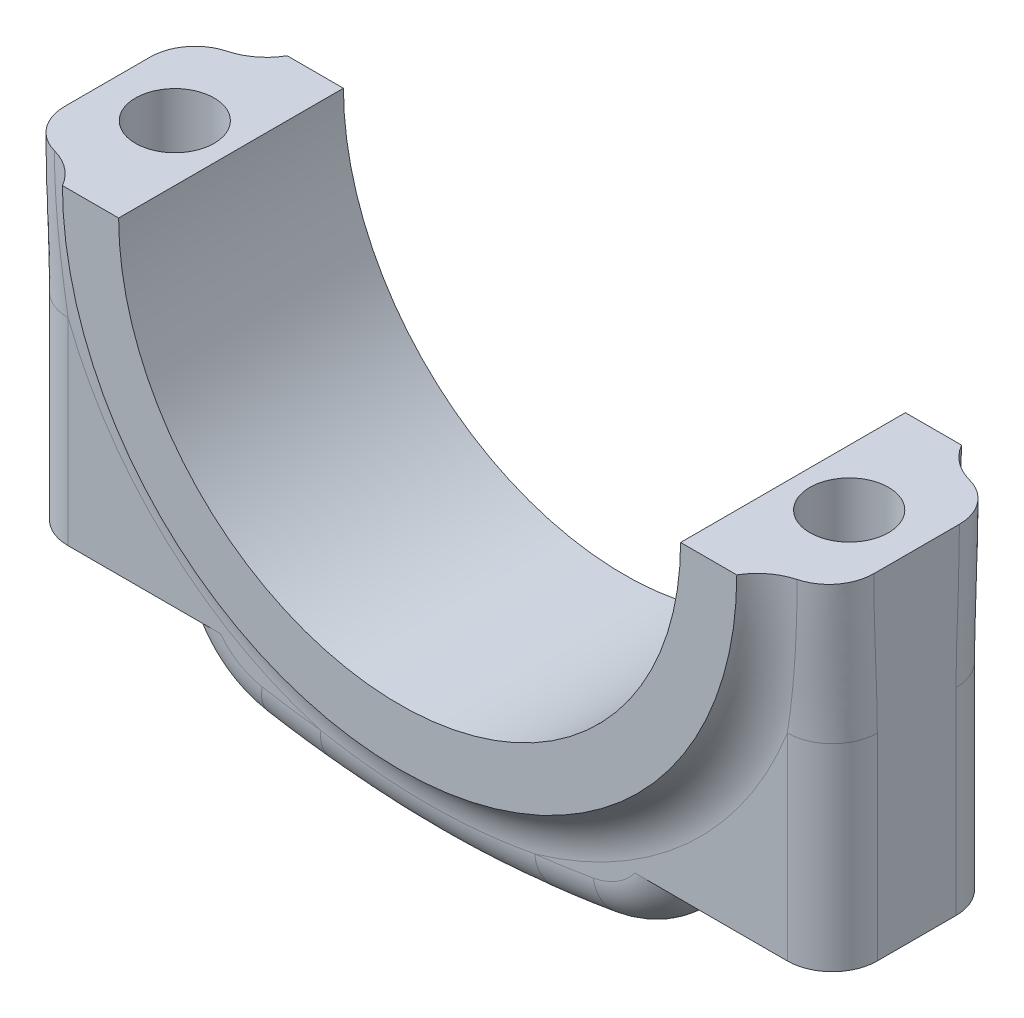
SolidWorks part; units mm, degrees
ref_plane "Front Plane" through (0, 0, 0) normal (0, 0, 1) x (1, 0, 0)
ref_plane "Top Plane" through (0, 0, 0) normal (0, 1, 0) x (1, 0, 0)
ref_plane "Right Plane" through (0, 0, 0) normal (1, 0, 0) x (0, 0, -1)
sketch "Sketch1" plane through (0, 0, 0) normal (0, 0, 1) x (1, 0, 0)
  line L0 (-36, 0) -> (-25, 0)
  line L1 (36, 0) -> (36, -30)
  line L2 (0, 0) -> (0, -25) construction
  line L3 (-36, 0) -> (-36, -30)
  line L4 (25, 0) -> (36, 0)
  arc A0 (-25, 0) -> (25, 0) centre (0, 0) ccw
  arc A1 (-36, -30) -> (36, -30) centre (0, 52.4864) ccw
  dimension "D3" = 50
  dimension "D4" = 180
  dimension "D1" = 36
  dimension "D2" = 30
extrude "Boss-Extrude1" add sketch "Sketch1" along normal mid plane 15
sketch "Sketch2" plane through (0, 0, 7.5) normal (0, 0, 1) x (1, 0, 0)
  line L0 (-30, 0) -> (-25, 0)
  line L1 (25, 0) -> (30, 0)
  arc A0 (-25, 0) -> (25, 0) centre (0, 0) ccw construction
  arc A1 (-25, 0) -> (25, 0) centre (0, 0) ccw
  arc A2 (-30, 0) -> (30, 0) centre (0, 0) ccw
  dimension "D1" = 60
extrude "Boss-Extrude2" add sketch "Sketch2" along normal blind 2.5
sketch "Sketch3" plane through (0, 0, -7.5) normal (0, 0, -1) x (-1, 0, 0)
  line L2 (30, 0) -> (25, 0)
  line L3 (-25, 0) -> (-30, 0)
  line L4 (30, 0) -> (25, 0)
  line L5 (-25, 0) -> (-30, 0)
  arc A2 (-25, 0) -> (25, 0) centre (0, 0) ccw
  arc A3 (-30, 0) -> (30, 0) centre (0, 0) ccw
  arc A4 (-25, 0) -> (25, 0) centre (0, 0) ccw
  arc A5 (-30, 0) -> (30, 0) centre (0, 0) ccw
  dimension "D1" = 0
extrude "Boss-Extrude3" add sketch "Sketch3" along normal blind 2.5
fillet "Fillet1" radius 5 2 edges at (0, -30, 7.5) (0, -30, -7.5)
hole_wizard "Ø7.0 (7) Diameter Hole1" positions "Sketch13" profile "Sketch14" hole size "Ø7.0" standard "ISO" end condition through all
sketch "Sketch13" plane through (0, 0, 0) normal (0, 1, 0) x (1, 0, 0)
  point P0 (30, 0)
  point P2 (-30, 0)
  dimension "D1" = 30
  dimension "D2" = 30
sketch "Sketch14" plane through (30, 0, 0) normal (1, 0, 0) x (0, 0, 1)
  line L0 (0, 0) -> (0, 37.5136)
  line L1 (0, 37.5136) -> (3.5, 37.5136)
  line L2 (3.5, 37.5136) -> (3.5, 0)
  line L5 (3.5, 0) -> (0, 0)
  line L11 (0, -6.35) -> (0, 107.95) construction
  dimension "Thru Hole Dia." = 7
  dimension "Thru Hole Depth" = 37.5136
ref_plane "Plane1" through (0, -30, 0) normal (0, 1, 0) x (1, 0, 0)
sketch "Sketch15" plane through (0, -30, 0) normal (0, 1, 0) x (1, 0, 0)
  line L0 (0, 0) -> (0, -14.9136) construction
  line L1 (23, -12.2006) -> (37.3058, -12.2006)
  line L2 (23, -12.2006) -> (23, 11.925)
  line L3 (23, 11.925) -> (37.3058, 11.925)
  line L4 (37.3058, -12.2006) -> (37.3058, 11.925)
  line L5 (-37.3058, -12.2006) -> (-37.3058, 11.925)
  line L6 (-23, 11.925) -> (-37.3058, 11.925)
  line L7 (-23, -12.2006) -> (-23, 11.925)
  line L8 (-23, -12.2006) -> (-37.3058, -12.2006)
  dimension "D1" = 23
extrude "Cut-Extrude1" cut sketch "Sketch15" against normal blind 10
fillet "Fillet2" radius 10 2 edges at (-23, -34.5251, 0) (23, -34.5251, 0)
fillet "Fillet3" radius 4 10 edges at (-20.0132, -34.085, 7.5) (20.0132, -34.085, 7.5) (-20.0132, -34.085, -7.5) (20.0132, -34.085, -7.5) (36, -15, -7.5) (-36, -15, 7.5) (-36, -15, -7.5) (0, -37.5136, 7.5) (0, -37.5136, -7.5) (36, -15, 7.5)
